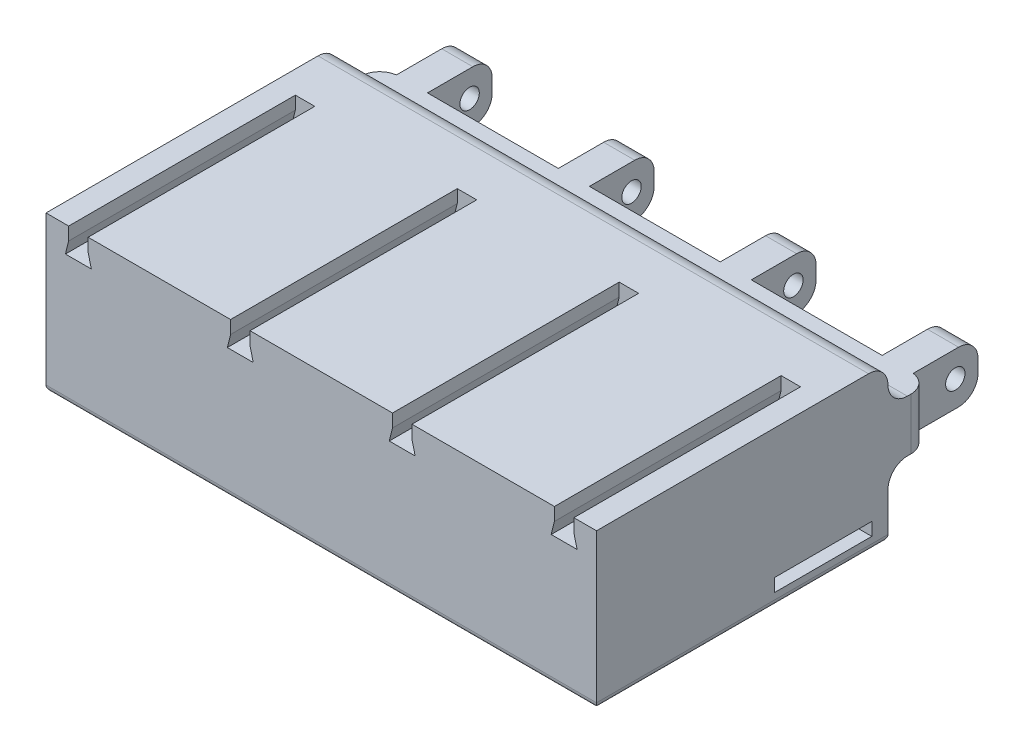
SolidWorks part; units mm, degrees
ref_plane "Alzado" through (0, 0, 0) normal (0, 0, 1) x (1, 0, 0)
ref_plane "Planta" through (0, 0, 0) normal (0, 1, 0) x (1, 0, 0)
ref_plane "Vista lateral" through (0, 0, 0) normal (1, 0, 0) x (0, 0, -1)
sketch "Croquis1" plane through (0, 0, 0) normal (1, 0, 0) x (0, 0, -1)
  line L0 (0, 9) -> (0, 1) construction
  line L9 (-1.5, 9) -> (-63, 9) construction
  line L18 (0, 9) -> (0, -9) construction
  line L19 (0, -9) -> (-63, -9) construction
  line L25 (0, 1) -> (-18, 1) construction
  line L26 (0, 1) -> (0, -2.6179) construction
  line L29 (0, -2.6179) -> (0, -9) construction
  line L31 (-1.5, 9) -> (-1.5, 1)
  line L32 (-18, 1) -> (-1.5, 1)
  line L35 (-63, -9) -> (-18, -9)
  line L56 (-63, 9) -> (-63, -9)
  line L59 (0, 9) -> (-63, 9) construction
  line L61 (-18, 1) -> (-18, -9)
  line L62 (-18, 9) -> (-18, 15)
  line L63 (-18, 15) -> (-63, 15)
  line L64 (-63, 15) -> (-63, 9)
  line L65 (-1.5, 9) -> (-18, 9)
  circle A0 centre (-5, 5) radius 1.5
  point P9 (0, 0)
  point P12 (0, 5)
  dimension "D6" = 3
  dimension "D1" = 16.5
  dimension "D2" = 10
  dimension "D3" = 45
  dimension "D4" = 8
  dimension "D5" = 6
  dimension "D7" = 5
  dimension "D8" = 3
extrude "Saliente-Extruir1" add sketch "Croquis1" along normal mid plane 85
sketch "Croquis2" plane through (0, 0, 0) normal (0, 1, 0) x (1, 0, 0)
  line L17 (42.5, -1.5) -> (-42.5, -1.5) construction
  line L18 (-39.9, -1.5) -> (-35.1, -1.5) construction
  line L19 (-39.9, -1.5) -> (-39.9, -11.5)
  line L20 (-39.9, -11.5) -> (-35.1, -11.5) construction
  line L21 (-35.1, -1.5) -> (-35.1, -11.5)
  line L23 (-14.9, -1.5) -> (-10.1, -1.5) construction
  line L24 (-14.9, -1.5) -> (-14.9, -11.5)
  line L25 (-14.9, -11.5) -> (-10.1, -11.5) construction
  line L26 (-10.1, -1.5) -> (-10.1, -11.5)
  line L27 (10.1, -1.5) -> (14.9, -1.5) construction
  line L28 (10.1, -1.5) -> (10.1, -11.5)
  line L29 (10.1, -11.5) -> (14.9, -11.5) construction
  line L30 (14.9, -1.5) -> (14.9, -11.5)
  line L31 (35.1, -1.5) -> (39.9, -1.5) construction
  line L32 (35.1, -1.5) -> (35.1, -11.5)
  line L33 (35.1, -11.5) -> (39.9, -11.5) construction
  line L34 (39.9, -1.5) -> (39.9, -11.5)
  line L39 (-39.9, -6.5) -> (39.9, -6.5) construction
  line L40 (14.9, -1.5) -> (35.1, -1.5)
  line L41 (14.9, -11.5) -> (35.1, -11.5)
  line L42 (-10.1, -1.5) -> (10.1, -1.5)
  line L43 (-10.1, -11.5) -> (10.1, -11.5)
  line L44 (-35.1, -11.5) -> (-14.9, -11.5)
  line L45 (-35.1, -1.5) -> (-14.9, -1.5)
  line L46 (-39.9, -1.5) -> (-42.5, -1.5)
  line L47 (-42.5, -1.5) -> (-42.5, -11.5)
  line L48 (-42.5, -11.5) -> (-39.9, -11.5)
  line L49 (39.9, -1.5) -> (42.5, -1.5)
  line L50 (42.5, -1.5) -> (42.5, -11.5)
  line L51 (42.5, -11.5) -> (39.9, -11.5)
  point P23 (-37.5, -11.5)
  point P24 (-12.5, -11.5)
  point P25 (12.5, -11.5)
  point P26 (37.5, -11.5)
  point P29 (0, -6.5)
  dimension "D1" = 4.8
  dimension "D2" = 25
  dimension "D3" = 25
  dimension "D4" = 25
  dimension "D5" = 10
extrude "Cortar-Extruir1" cut sketch "Croquis2" against normal through all both and the other way through all
sketch "Croquis4" plane through (0, 0, 0) normal (1, 0, 0) x (0, 0, -1)
  line L5 (-63, -9) -> (-18, -9) construction
  line L7 (-18, -9) -> (-18, 1) construction
  line L8 (-35.5, -5) -> (-20.5, -5)
  line L9 (-35.5, -5) -> (-35.5, -7)
  line L10 (-35.5, -7) -> (-20.5, -7)
  line L11 (-20.5, -5) -> (-20.5, -7)
  point P7 (-28, -7)
  dimension "D1" = 2
  dimension "D2" = 2
  dimension "D3" = 15
  dimension "D4" = 10
extrude "Cortar-Extruir4" cut sketch "Croquis4" against normal through all both and the other way through all
fillet "Redondeo3" radius 3 13 edges at (-37.5, 9, 1.5) (-37.5, 1, 1.5) (37.5, 9, 1.5) (37.5, 1, 1.5) (12.5, 9, 1.5) (12.5, 1, 1.5) (-12.5, 9, 1.5) (-12.5, 1, 1.5) (0, 1, 18) (0, 9, 18) (42.5, 5, 11.5) (-42.5, 5, 11.5) (0, 15, 18)
sketch "Croquis5" plane through (0, 0, 63) normal (0, 0, -1) x (-1, 0, 0)
  line L0 (10.1, 9) -> (14.9, 9) construction
  line L21 (37.5, 9) -> (37.5, 15) construction
  line L22 (35.1, 9) -> (39.9, 9) construction
  line L23 (-12.5, 9) -> (-12.5, 15) construction
  line L24 (-14.9, 9) -> (-10.1, 9) construction
  line L25 (-37.5, 9) -> (-37.5, 15) construction
  line L26 (-39.9, 9) -> (-35.1, 9) construction
  line L27 (12.5, 9) -> (12.5, 15) construction
  line L28 (11, 13) -> (10.5, 11)
  line L29 (11, 15) -> (14, 15)
  line L30 (11, 15) -> (11, 13)
  line L31 (11, 13) -> (14, 13) construction
  line L32 (14, 15) -> (14, 13)
  line L33 (10.5, 11) -> (14.5, 11)
  line L34 (14.5, 11) -> (14, 13)
  line L35 (-39, 13) -> (-39.5, 11)
  line L36 (36, 15) -> (39, 15)
  line L37 (36, 15) -> (36, 13)
  line L38 (36, 13) -> (39, 13) construction
  line L39 (39, 15) -> (39, 13)
  line L40 (-36, 15) -> (-39, 15)
  line L41 (-36, 15) -> (-36, 13)
  line L42 (-36, 13) -> (-39, 13) construction
  line L43 (-39, 15) -> (-39, 13)
  line L44 (-11, 15) -> (-14, 15)
  line L45 (-11, 15) -> (-11, 13)
  line L46 (-11, 13) -> (-14, 13) construction
  line L47 (-14, 15) -> (-14, 13)
  line L48 (-39.5, 11) -> (-35.5, 11)
  line L49 (-35.5, 11) -> (-36, 13)
  line L50 (-14, 13) -> (-14.5, 11)
  line L51 (-14.5, 11) -> (-10.5, 11)
  line L52 (-10.5, 11) -> (-11, 13)
  line L53 (36, 13) -> (35.5, 11)
  line L54 (35.5, 11) -> (39.5, 11)
  line L55 (39.5, 11) -> (39, 13)
  line L56 (-42.5, 15) -> (42.5, 15) construction
  point P12 (12.5, 15)
  point P30 (37.5, 15)
  point P39 (-12.5, 15)
  point P40 (-37.5, 15)
  dimension "D1" = 3
  dimension "D2" = 2
  dimension "D3" = 2
  dimension "D4" = 4
  dimension "D5" = 2
  dimension "D8" = 2
  dimension "D9" = 2
extrude "Cortar-Extruir6" cut sketch "Croquis5" along normal blind 35
fillet "Redondeo2" radius 1 4 edges at (42.5, -9, 40.5) (-42.5, -9, 40.5) (0, -9, 63) (0, -9, 18)
